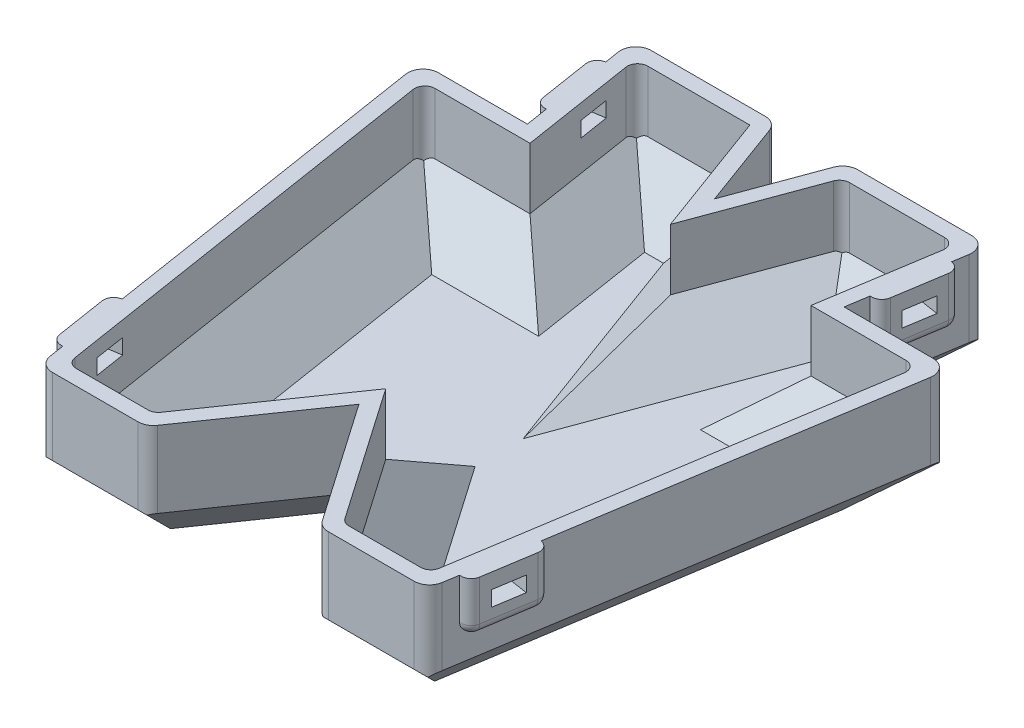
SolidWorks part; units mm, degrees
ref_plane "Front Plane" through (0, 0, 0) normal (0, 0, 1) x (1, 0, 0)
ref_plane "Top Plane" through (0, 0, 0) normal (0, 1, 0) x (1, 0, 0)
ref_plane "Right Plane" through (0, 0, 0) normal (1, 0, 0) x (0, 0, -1)
sketch "Sketch1" plane through (0, 0, 0) normal (0, 1, 0) x (1, 0, 0)
  line L0 (-35, 83.6369) -> (-7, 83.6369)
  line L1 (-7, 83.6369) -> (0, 64.6242)
  line L2 (-35, 83.6369) -> (-17.1111, -29.9632) construction
  line L3 (-14, 83.6369) -> (0, -5.2675) construction
  line L4 (0, 89.978) -> (0, -98.0426) construction
  line L5 (-48.6017, 55.9412) -> (-35.5466, -26.9632)
  line L6 (-31.1111, 58.9412) -> (-52.1111, 58.9412)
  line L7 (-17.1111, -29.9632) -> (-38.1111, -29.9632)
  line L8 (-52.1111, 58.9412) -> (-38.1111, -29.9632)
  line L9 (-35.5466, -26.9632) -> (-18.6822, -26.9632)
  line L10 (-18.6822, -26.9632) -> (0, 0)
  line L11 (0, -5.2675) -> (-17.1111, -29.9632)
  line L13 (14, 83.6369) -> (0, -5.2675) construction
  line L14 (0, -5.2675) -> (17.1111, -29.9632)
  line L17 (52.1111, 58.9412) -> (38.1111, -29.9632)
  line L18 (17.1111, -29.9632) -> (38.1111, -29.9632)
  line L19 (31.1111, 58.9412) -> (52.1111, 58.9412)
  line L20 (35, 83.6369) -> (17.1111, -29.9632) construction
  line L21 (7, 83.6369) -> (0, 64.6242)
  line L22 (35, 83.6369) -> (7, 83.6369)
  line L27 (0, 55.9412) -> (-9.0923, 80.6369)
  line L28 (-9.0923, 80.6369) -> (-31.4906, 80.6369)
  line L29 (-31.4906, 80.6369) -> (-27.6017, 55.9412)
  line L30 (-27.6017, 55.9412) -> (-48.6017, 55.9412)
  line L31 (18.6822, -26.9632) -> (0, 0)
  line L32 (35.5466, -26.9632) -> (18.6822, -26.9632)
  line L33 (48.6017, 55.9412) -> (35.5466, -26.9632)
  line L34 (27.6017, 55.9412) -> (48.6017, 55.9412)
  line L35 (31.4906, 80.6369) -> (27.6017, 55.9412)
  line L36 (9.0923, 80.6369) -> (31.4906, 80.6369)
  line L37 (0, 55.9412) -> (9.0923, 80.6369)
  line L38 (-35, 83.6369) -> (-31.1111, 58.9412)
  line L39 (35, 83.6369) -> (31.1111, 58.9412)
  line L40 (0, 0) -> (0, -5.2675)
  point P4 (-14, 83.6369)
  point P30 (14, 83.6369)
  dimension "D1" = 90
  dimension "D2" = 21
  dimension "D3" = 7
  dimension "D4" = 21
  dimension "D5" = 90
  dimension "D6" = 25
  dimension "D7" = 21
  dimension "D8" = 3
  dimension "D9" = 35
  dimension "D10" = 3
  dimension "D11" = 3
  dimension "D12" = 3
  dimension "D13" = 3
  dimension "D14" = 3
  dimension "D15" = 3
extrude "Boss-Extrude2" add sketch "Sketch1" along normal blind 25 contours L27 L37 L36 L35 L34 L33 L32 L31 L14 L18 L17 L19 L39 L22 L21 L1 L0 L38 L6 L8 L7 L11 L10 L9 L5 L30 L29 L28 region at (-21, 0, -82.0953)
extrude "Boss-Extrude5" add sketch "Sketch1<7>" along normal blind 3 contours L37 L27 L28 L29 L30 L5 L9 L10 L31 L32 L33 L34 L35 L36 region at (0, 0, -27.1018)
sketch "Sketch1<7>" plane through (0, 0, 0) normal (0, 1, 0) x (1, 0, 0) same geometry as "Sketch1"
chamfer "Chamfer2" distance 10 angle 45 28 edges at (27.1144, 3, 26.9632) (9.3411, 3, 13.4816) (-9.3411, 3, 13.4816) (-27.1144, 3, 26.9632) (42.0741, 3, -14.489) (38.1017, 3, -55.9412) (29.5462, 3, -68.2891) (20.2915, 3, -80.6369) (4.5462, 3, -68.2891) (-4.5462, 3, -68.2891) (-20.2915, 3, -80.6369) (-29.5462, 3, -68.2891) (-42.0741, 3, -14.489) (-38.1017, 3, -55.9412) (-3.5, 0, -74.1306) (3.5, 0, -74.1306) (21, 0, -83.6369) (33.0556, 0, -71.2891) (41.6111, 0, -58.9412) (45.1111, 0, -14.489) (27.6111, 0, 29.9632) (8.5556, 0, 17.6154) (-8.5556, 0, 17.6154) (-27.6111, 0, 29.9632) (-45.1111, 0, -14.489) (-41.6111, 0, -58.9412) (-33.0556, 0, -71.2891) (-21, 0, -83.6369)
fillet "Fillet4" radius 3 10 edges at (-38.1111, 17.5, 29.9632) (-17.1111, 17.5, 29.9632) (38.1111, 17.5, 29.9632) (17.1111, 17.5, 29.9632) (52.1111, 17.5, -58.9412) (35, 17.5, -83.6369) (7, 17.5, -83.6369) (-7, 17.5, -83.6369) (-52.1111, 17.5, -58.9412) (-35, 17.5, -83.6369)
fillet "Fillet5" radius 2 9 edges at (-18.6822, 19, 26.9632) (18.6822, 19, 26.9632) (35.5466, 19, 26.9632) (48.6017, 19, -55.9412) (31.4906, 19, -80.6369) (9.0923, 19, -80.6369) (-31.4906, 19, -80.6369) (-48.6017, 19, -55.9412) (-35.5466, 19, 26.9632)
sketch "Sketch5" plane through (-21.3013, 0, 3.3544) normal (-0.9878, 0, 0.1556) x (0.1556, 0, 0.9878)
  line L0 (-84.5539, 25) -> (-63.0633, 25) construction
  line L1 (-67.5539, 15) -> (-81.5539, 15)
  line L2 (-67.5539, 15) -> (-67.5539, 25)
  line L3 (-67.5539, 25) -> (-81.5539, 25)
  line L4 (-81.5539, 15) -> (-81.5539, 25)
  line L5 (-67.5539, 15) -> (-81.5539, 25) construction
  line L6 (-67.5539, 25) -> (-81.5539, 15) construction
  line L7 (-84.5539, 25) -> (-84.5539, 10) construction
  line L9 (-71.5539, 17.8571) -> (-77.5539, 17.8571) construction
  line L10 (-71.5539, 17.8571) -> (-71.5539, 22.1429) construction
  line L11 (-71.5539, 22.1429) -> (-77.5539, 22.1429) construction
  line L12 (-77.5539, 17.8571) -> (-77.5539, 22.1429) construction
  line L13 (-71.5539, 17.8571) -> (-77.5539, 22.1429) construction
  line L14 (-71.5539, 22.1429) -> (-77.5539, 17.8571) construction
  point P0 (-74.5539, 20)
  point P9 (-74.5539, 20)
  dimension "D1" = 14
  dimension "D2" = 10
  dimension "D3" = 3
  dimension "D4" = 6
extrude "Boss-Extrude6" add sketch "Sketch5" along normal blind 2
sketch "Sketch6" plane through (-23.2769, 0, 3.6655) normal (-0.9878, 0, 0.1556) x (0.1556, 0, 0.9878)
  line L0 (-67.5539, 25) -> (-81.5539, 25) construction
  line L1 (-71.5539, 19) -> (-77.5539, 19)
  line L2 (-71.5539, 19) -> (-71.5539, 22)
  line L3 (-71.5539, 22) -> (-77.5539, 22)
  line L4 (-77.5539, 19) -> (-77.5539, 22)
  line L5 (-71.5539, 19) -> (-77.5539, 22) construction
  line L6 (-71.5539, 22) -> (-77.5539, 19) construction
  line L7 (-67.5539, 15) -> (-67.5539, 25) construction
  point P0 (-74.5539, 20.5)
  dimension "D1" = 3
  dimension "D2" = 4
  dimension "D3" = 6
  dimension "D4" = 3
extrude "Cut-Extrude5" cut sketch "Sketch6" against normal up to surface (5 mm away) up to face at (-29.3642, 19, -67.1335)
sketch "Sketch7" plane through (-41.7931, 0, 6.5813) normal (-0.9878, 0, 0.1556) x (0.1556, 0, 0.9878)
  line L0 (18.1055, 15) -> (4.1055, 15)
  line L1 (18.1055, 15) -> (18.1055, 25)
  line L2 (18.1055, 25) -> (4.1055, 25)
  line L3 (4.1055, 15) -> (4.1055, 25)
  line L4 (18.1055, 15) -> (4.1055, 25) construction
  line L5 (18.1055, 25) -> (4.1055, 15) construction
  line L6 (8.1055, 22.1429) -> (14.1055, 22.1429) construction
  line L7 (8.1055, 22.1429) -> (8.1055, 17.8571) construction
  line L8 (8.1055, 17.8571) -> (14.1055, 17.8571) construction
  line L9 (14.1055, 22.1429) -> (14.1055, 17.8571) construction
  line L10 (8.1055, 22.1429) -> (14.1055, 17.8571) construction
  line L11 (8.1055, 17.8571) -> (14.1055, 22.1429) construction
  line L12 (21.1055, 10) -> (21.1055, 25) construction
  line L13 (-62.8205, 25) -> (21.1055, 25) construction
  point P0 (11.1055, 20)
  point P5 (11.1055, 20)
  dimension "D1" = 14
  dimension "D2" = 10
  dimension "D3" = 6
  dimension "D4" = 3
extrude "Boss-Extrude7" add sketch "Sketch7" along normal blind 2
sketch "Sketch8" plane through (-43.7688, 0, 6.8924) normal (-0.9878, 0, 0.1556) x (0.1556, 0, 0.9878)
  line L0 (18.1055, 15) -> (18.1055, 25) construction
  line L1 (8.1055, 19) -> (14.1055, 19)
  line L2 (8.1055, 19) -> (8.1055, 22)
  line L3 (8.1055, 22) -> (14.1055, 22)
  line L4 (14.1055, 19) -> (14.1055, 22)
  line L5 (8.1055, 19) -> (14.1055, 22) construction
  line L6 (8.1055, 22) -> (14.1055, 19) construction
  line L7 (18.1055, 25) -> (4.1055, 25) construction
  point P0 (11.1055, 20.5)
  dimension "D1" = 3
  dimension "D2" = 6
  dimension "D3" = 4
  dimension "D4" = 3
extrude "Cut-Extrude6" cut sketch "Sketch8" against normal up to surface (5 mm away) up to face at (-42.0252, 19, -14.1779)
ref_plane "Plane1" through (0, 0, 0) normal (-1, 0, 0) x (0, 0, 1)
mirror "Mirror1" about plane through (0, 0, 0) normal (-1, 0, 0) of "Boss-Extrude7", "Boss-Extrude6"
sketch "Sketch9" plane through (43.7688, 0, 6.8924) normal (0.9878, 0, 0.1556) x (0.1556, 0, -0.9878)
  line L0 (-18.1055, 25) -> (-4.1055, 25) construction
  line L1 (-8.1055, 19) -> (-14.1055, 19)
  line L2 (-8.1055, 19) -> (-8.1055, 22)
  line L3 (-8.1055, 22) -> (-14.1055, 22)
  line L4 (-14.1055, 19) -> (-14.1055, 22)
  line L5 (-8.1055, 19) -> (-14.1055, 22) construction
  line L6 (-8.1055, 22) -> (-14.1055, 19) construction
  line L7 (-4.1055, 25) -> (-4.1055, 15) construction
  point P0 (-11.1055, 20.5)
  dimension "D1" = 3
  dimension "D2" = 6
  dimension "D3" = 3
  dimension "D4" = 4
extrude "Cut-Extrude7" cut sketch "Sketch9" against normal up to surface (5 mm away) up to face at (42.0252, 19, -14.1779)
sketch "Sketch10" plane through (23.2769, 0, 3.6655) normal (0.9878, 0, 0.1556) x (0.1556, 0, -0.9878)
  line L0 (67.5539, 25) -> (81.5539, 25) construction
  line L1 (77.5539, 19) -> (71.5539, 19)
  line L2 (77.5539, 19) -> (77.5539, 22)
  line L3 (77.5539, 22) -> (71.5539, 22)
  line L4 (71.5539, 19) -> (71.5539, 22)
  line L5 (77.5539, 19) -> (71.5539, 22) construction
  line L6 (77.5539, 22) -> (71.5539, 19) construction
  line L7 (81.5539, 25) -> (81.5539, 15) construction
  point P0 (74.5539, 20.5)
  dimension "D1" = 3
  dimension "D2" = 4
  dimension "D3" = 6
  dimension "D4" = 3
extrude "Cut-Extrude8" cut sketch "Sketch10" against normal up to surface (5 mm away) up to face at (29.3642, 19, -67.1335)
fillet "Fillet7" radius 2 12 edges at (-40.9524, 20, 24.7775) (-42.0413, 15, 17.8627) (-43.1301, 20, 10.9479) (-33.7853, 20, -63.0661) (-34.8742, 15, -69.9809) (-35.9631, 20, -76.8957) (35.9631, 20, -76.8957) (33.7853, 20, -63.0661) (34.8742, 15, -69.9809) (43.1301, 20, 10.9479) (40.9524, 20, 24.7775) (42.0413, 15, 17.8627)
